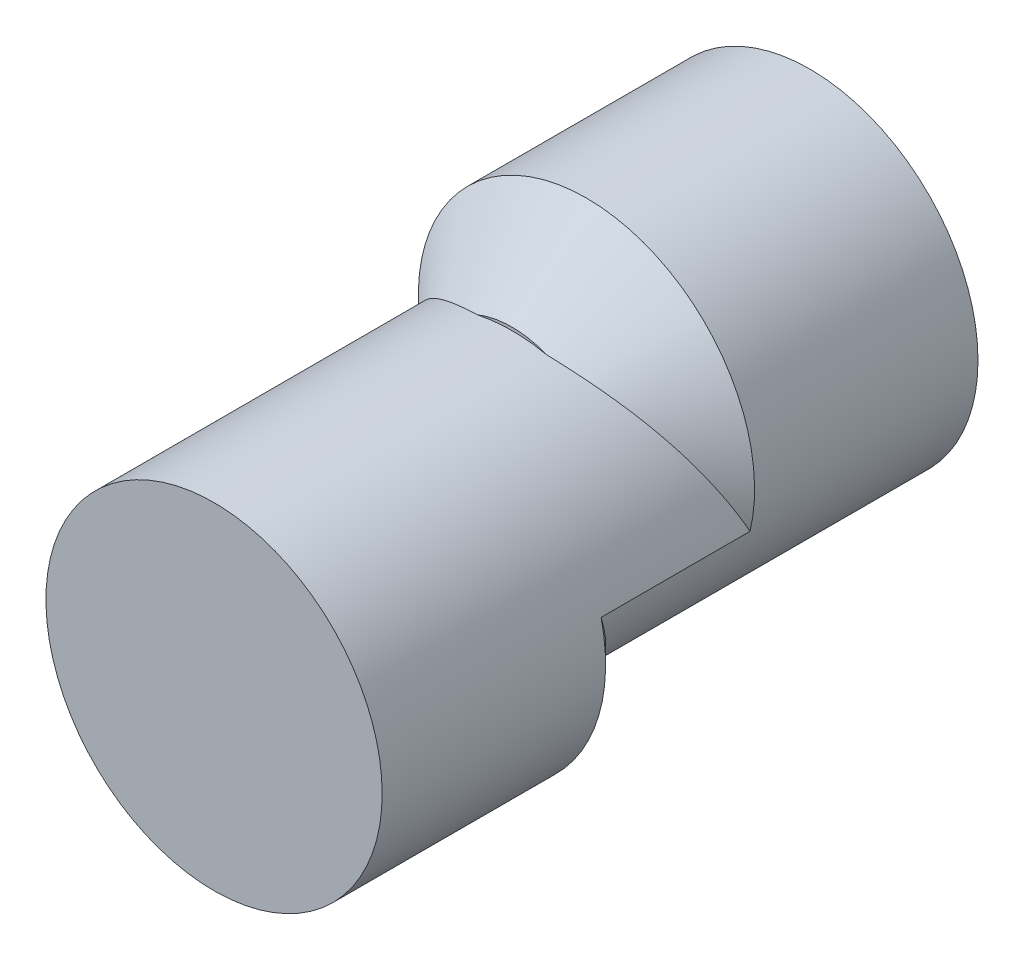
SolidWorks part; units mm, degrees
ref_plane "Plan de face" through (0, 0, 0) normal (0, 0, 1) x (1, 0, 0)
ref_plane "Plan de dessus" through (0, 0, 0) normal (0, 1, 0) x (1, 0, 0)
ref_plane "Plan de droite" through (0, 0, 0) normal (1, 0, 0) x (0, 0, -1)
sketch "Esquisse1" plane through (0, 0, 0) normal (0, 0, 1) x (1, 0, 0)
  circle A1 centre (0, 0.8221) radius 3.95
  dimension "D3" = 7.9
extrude "Boss.-Extru.1" add sketch "Esquisse1" along normal blind 7
sketch "Esquisse2" plane through (0, 0, 7) normal (0, 0, 1) x (1, 0, 0)
  circle A0 centre (0, -1) radius 3.95
  dimension "D1" = 7.9
  dimension "D2" = 1
extrude "Boss.-Extru.2" add sketch "Esquisse2" along normal blind 7
sketch "Esquisse3" plane through (0, 0, 14) normal (0, 0, 1) x (1, 0, 0)
  line L0 (-1.5, 2) -> (1.5, 2) construction
  line L1 (-1.5652, 2.2) -> (1.5652, 2.2)
  arc A0 (-1.5, 2) -> (1.5, 2) centre (0, 0) ccw construction
  arc A1 (-1.5652, 2.2) -> (1.5652, 2.2) centre (0, 0) ccw
  dimension "D1" = 5
  dimension "D2" = 2
  dimension "D3" = 0.2
extrude "Enlèv. mat.-Extru.1" cut sketch "Esquisse3" against normal through all from offset 2 offset against normal yes
chamfer "Chanfrein2" distance 1.75 angle 45 1 edges at (0, 4.7721, 7)
chamfer "Chanfrein4" distance 1.75 angle 45 1 edges at (0, -4.95, 7)
